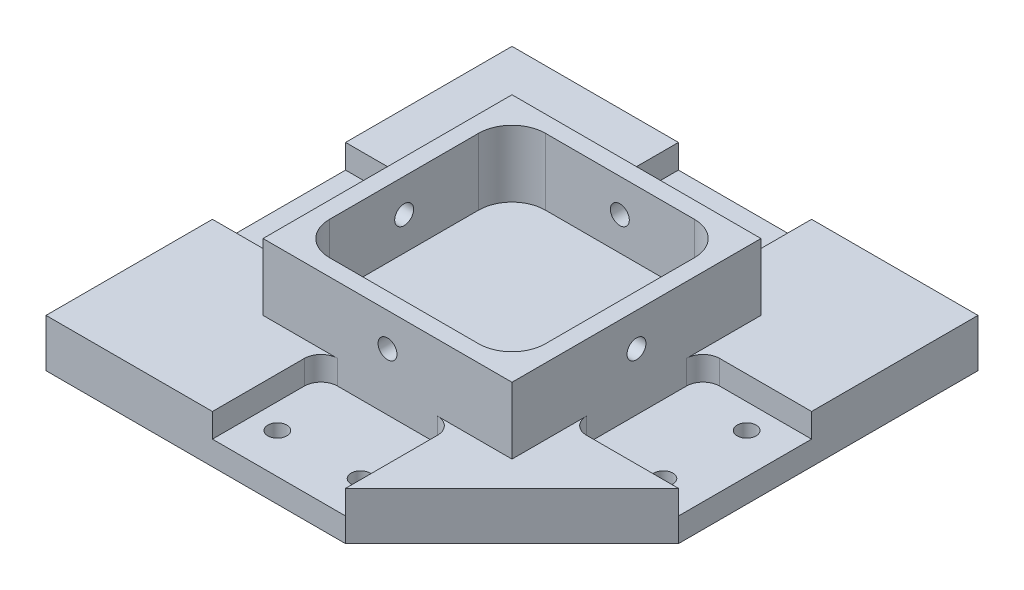
SolidWorks part; units mm, degrees
material "6061 Alloy"
ref_plane "Front Plane" through (0, 0, 0) normal (0, 0, 1) x (1, 0, 0)
ref_plane "Top Plane" through (0, 0, 0) normal (0, 1, 0) x (1, 0, 0)
ref_plane "Right Plane" through (0, 0, 0) normal (1, 0, 0) x (0, 0, -1)
sketch "Sketch1" plane through (0, 0, 0) normal (0, 1, 0) x (1, 0, 0)
  line L1 (0, 0) -> (88.9, 0)
  line L2 (0, 0) -> (0, 88.9)
  line L3 (0, 88.9) -> (88.9, 88.9)
  line L4 (88.9, 0) -> (88.9, 88.9)
  dimension "D1" = 88.9
  dimension "D2" = 88.9
extrude "Boss-Extrude1" add sketch "Sketch1" along normal blind 9.144
sketch "Sketch2" plane through (0, 9.144, 0) normal (0, 1, 0) x (1, 0, 0)
  line L0 (88.9, 88.9) -> (0, 88.9) construction
  line L1 (31.75, 88.9) -> (57.15, 88.9)
  line L2 (31.75, 88.9) -> (31.75, 67.31)
  line L3 (31.75, 67.31) -> (57.15, 67.31)
  line L4 (57.15, 88.9) -> (57.15, 67.31)
  line L5 (0, 88.9) -> (0, 0) construction
  line L6 (0, 57.15) -> (21.59, 57.15)
  line L7 (0, 57.15) -> (0, 31.75)
  line L8 (0, 31.75) -> (21.59, 31.75)
  line L9 (21.59, 57.15) -> (21.59, 31.75)
  line L10 (0, 0) -> (88.9, 0) construction
  line L11 (31.75, 0) -> (57.15, 0)
  line L12 (31.75, 0) -> (31.75, 21.59)
  line L13 (31.75, 21.59) -> (57.15, 21.59)
  line L14 (57.15, 0) -> (57.15, 21.59)
  line L15 (88.9, 0) -> (88.9, 88.9) construction
  line L16 (88.9, 57.15) -> (67.31, 57.15)
  line L17 (88.9, 57.15) -> (88.9, 31.75)
  line L18 (88.9, 31.75) -> (67.31, 31.75)
  line L19 (67.31, 57.15) -> (67.31, 31.75)
  dimension "D1" = 31.75
  dimension "D2" = 25.4
  dimension "D3" = 25.4
  dimension "D4" = 31.75
  dimension "D5" = 25.4
  dimension "D6" = 31.75
  dimension "D7" = 25.4
  dimension "D8" = 31.75
  dimension "D9" = 21.59
  dimension "D10" = 21.59
  dimension "D11" = 21.59
  dimension "D12" = 21.59
extrude "Cut-Extrude1" cut sketch "Sketch2" against normal blind 4.572
sketch "Sketch3" plane through (0, 9.144, 0) normal (0, 1, 0) x (1, 0, 0)
  line L0 (31.75, 88.9) -> (0, 88.9) construction
  line L1 (20.6375, 68.2625) -> (68.2625, 68.2625)
  line L2 (20.6375, 68.2625) -> (20.6375, 20.6375)
  line L3 (20.6375, 20.6375) -> (68.2625, 20.6375)
  line L4 (68.2625, 68.2625) -> (68.2625, 20.6375)
  line L5 (0, 31.75) -> (0, 0) construction
  line L6 (88.9, 31.75) -> (88.9, 57.15) construction
  line L7 (57.15, 88.9) -> (31.75, 88.9) construction
  line L8 (0, 57.15) -> (0, 31.75) construction
  line L9 (31.75, 0) -> (57.15, 0) construction
  circle A0 centre (28.194, 44.45) radius 2.4
  circle A1 centre (44.45, 60.706) radius 2.4
  circle A2 centre (60.706, 44.45) radius 2.4
  circle A3 centre (44.45, 28.194) radius 2.4
  dimension "D5" = 4.8
  dimension "D6" = 4.8
  dimension "D7" = 4.8
  dimension "D8" = 4.8
  dimension "D1" = 47.625
  dimension "D2" = 47.625
  dimension "D3" = 20.6375
  dimension "D4" = 20.6375
  dimension "D9" = 28.194
  dimension "D10" = 28.194
  dimension "D11" = 28.194
  dimension "D12" = 28.194
  dimension "D13" = 23.8125
  dimension "D14" = 23.8125
  dimension "D15" = 23.8125
  dimension "D16" = 23.8125
extrude "Cut-Extrude2" [suppressed] cut sketch "Sketch3" against normal through all contours A2 | A1 | A0 | A3
sketch "Sketch4" plane through (0, 4.572, 0) normal (0, 1, 0) x (1, 0, 0)
  line L0 (0, 57.15) -> (0, 31.75) construction
  line L1 (57.15, 88.9) -> (31.75, 88.9) construction
  line L2 (88.9, 31.75) -> (88.9, 57.15) construction
  line L3 (31.75, 0) -> (57.15, 0) construction
  line L4 (0, 31.75) -> (21.59, 31.75) construction
  line L5 (31.75, 21.59) -> (31.75, 0) construction
  line L6 (67.31, 31.75) -> (88.9, 31.75) construction
  line L7 (57.15, 67.31) -> (57.15, 88.9) construction
  circle A0 centre (81.28, 52.3875) radius 1.8034
  circle A1 centre (81.28, 36.5125) radius 1.8034
  circle A2 centre (52.3875, 81.28) radius 1.8034
  circle A3 centre (36.5125, 81.28) radius 1.8034
  circle A4 centre (7.62, 52.3875) radius 1.8034
  circle A5 centre (7.62, 36.5125) radius 1.8034
  circle A6 centre (36.5125, 7.62) radius 1.8034
  circle A7 centre (52.3875, 7.62) radius 1.8034
  dimension "D1" = 3.6068
  dimension "D2" = 3.6068
  dimension "D3" = 3.6068
  dimension "D4" = 3.6068
  dimension "D5" = 3.6068
  dimension "D6" = 3.6068
  dimension "D7" = 3.6068
  dimension "D8" = 3.6068
  dimension "D9" = 7.62
  dimension "D10" = 7.62
  dimension "D11" = 7.62
  dimension "D12" = 7.62
  dimension "D13" = 7.62
  dimension "D14" = 7.62
  dimension ".313" = 7.62
  dimension "D16" = 7.62
  dimension "D17" = 15.875
  dimension "D18" = 4.7625
  dimension "D19" = 4.7625
  dimension "D20" = 15.875
  dimension "D21" = 4.7625
  dimension "D22" = 15.875
  dimension "D23" = 4.7625
  dimension "D24" = 15.875
extrude "Cut-Extrude3" cut sketch "Sketch4" against normal through all
sketch "Sketch5" plane through (0, 9.144, 0) normal (0, 1, 0) x (1, 0, 0)
  line L0 (88.9, 88.9) -> (57.15, 88.9) construction
  line L1 (88.9, 31.75) -> (88.9, 57.15) construction
  circle A0 centre (44.45, 44.45) radius 6.35
  dimension "D1" = 12.7
  dimension "D2" = 44.45
  dimension "D3" = 44.45
extrude "Cut-Extrude4" [suppressed] cut sketch "Sketch5" against normal through all
sketch "Sketch6" plane through (0, 9.144, 0) normal (0, 1, 0) x (1, 0, 0)
  line L0 (88.9, 31.75) -> (57.15, 0)
  line L1 (57.15, 0) -> (88.9, 0)
  line L2 (88.9, 0) -> (88.9, 31.75)
extrude "Cut-Extrude5" cut sketch "Sketch6" against normal through all
sketch "Sketch7" plane through (0, 9.144, 0) normal (0, 1, 0) x (1, 0, 0)
  line L0 (0, 88.9) -> (0, 57.15) construction
  line L1 (20.701, 68.199) -> (68.199, 68.199)
  line L2 (20.701, 68.199) -> (20.701, 20.701)
  line L3 (20.701, 20.701) -> (68.199, 20.701)
  line L4 (68.199, 68.199) -> (68.199, 20.701)
  line L5 (0, 0) -> (31.75, 0) construction
  line L7 (23.876, 23.876) -> (65.024, 23.876)
  line L8 (23.876, 23.876) -> (23.876, 65.024)
  line L9 (23.876, 65.024) -> (65.024, 65.024)
  line L10 (65.024, 23.876) -> (65.024, 65.024)
  dimension "D1" = 47.498
  dimension "D2" = 47.498
  dimension "D3" = 20.701
  dimension "D4" = 20.701
  dimension "D5" = 3.175
  dimension "D6" = 3.175
  dimension "D7" = 3.175
  dimension "D8" = 3.175
extrude "Boss-Extrude2" add sketch "Sketch7" along normal blind 12.7 and the other way up to next (4.572 mm away)
fillet "Fillet9" radius 6.35 1 edges at (65.024, 15.494, -23.876)
fillet "Fillet10" radius 6.35 1 edges at (23.876, 15.494, -23.876)
fillet "Fillet11" radius 6.35 1 edges at (65.024, 15.494, -65.024)
fillet "Fillet12" radius 6.35 1 edges at (23.876, 15.494, -65.024)
fillet "Fillet15" radius 3.175 1 edges at (20.701, 6.858, -57.15)
fillet "Fillet16" radius 3.175 1 edges at (31.75, 6.858, -20.701)
fillet "Fillet17" radius 3.175 1 edges at (57.15, 6.858, -20.701)
fillet "Fillet18" radius 3.175 1 edges at (68.199, 6.858, -57.15)
fillet "Fillet19" radius 3.175 1 edges at (68.199, 6.858, -31.75)
fillet "Fillet20" radius 3.175 1 edges at (31.75, 6.858, -68.199)
fillet "Fillet21" radius 3.175 1 edges at (57.15, 6.858, -68.199)
fillet "Fillet22" radius 3.175 1 edges at (20.701, 6.858, -31.75)
sketch "Sketch9" plane through (0, 0, -68.199) normal (0, 0, -1) x (-1, 0, 0)
  line L0 (-68.199, 21.844) -> (-68.199, 9.144) construction
  line L1 (-68.199, 21.844) -> (-20.701, 21.844) construction
  circle A0 centre (-44.45, 15.494) radius 1.8034
  dimension "D1" = 3.6068
  dimension "D2" = 23.749
  dimension "D3" = 6.35
extrude "Cut-Extrude6" cut sketch "Sketch9" against normal through all
sketch "Sketch10" plane through (68.199, 0, 0) normal (1, 0, 0) x (0, 0, -1)
  line L0 (20.701, 21.844) -> (68.199, 21.844) construction
  line L1 (20.701, 21.844) -> (20.701, 9.144) construction
  circle A0 centre (44.45, 15.494) radius 1.8034
  dimension "D1" = 3.6068
  dimension "D2" = 6.35
  dimension "D3" = 23.749
extrude "Cut-Extrude7" cut sketch "Sketch10" against normal through all
equation "\"hinge_hole\"= 0.142in"
equation "\"D1@Sketch4\"=\"hinge_hole\""
equation "\"D2@Sketch4\"=\"hinge_hole\""
equation "\"D3@Sketch4\"=\"hinge_hole\""
equation "\"D4@Sketch4\"=\"hinge_hole\""
equation "\"D5@Sketch4\"=\"hinge_hole\""
equation "\"D6@Sketch4\"=\"hinge_hole\""
equation "\"D7@Sketch4\"=\"hinge_hole\""
equation "\"D8@Sketch4\"=\"hinge_hole\""
equation "\"hinge_hole_dist\"= 0.297 + 0.25"
equation "\".313@Sketch4\"=.3"
equation "\"hinge_hole_sep\"= 0.625"
equation "\"hinge_hole_from_wall\"= ( 1 - \"hinge_hole_sep\" ) / 2"
equation "\"D17@Sketch4\"=\"hinge_hole_sep\""
equation "\"D18@Sketch4\"=\"hinge_hole_from_wall\""
equation "\"D19@Sketch4\"=\"hinge_hole_from_wall\""
equation "\"D20@Sketch4\"=\"hinge_hole_sep\""
equation "\"D21@Sketch4\"=\"hinge_hole_from_wall\""
equation "\"D22@Sketch4\"=\"hinge_hole_sep\""
equation "\"D23@Sketch4\"=\"hinge_hole_from_wall\""
equation "\"D24@Sketch4\"=\"hinge_hole_sep\""
equation "\"D9@Sketch2\"=\"hinge_hole_dist\" + (0.6-0.297)"
equation "\"D12@Sketch2\"=\"hinge_hole_dist\" + (0.6-0.297)"
equation "\"D11@Sketch2\"=\"hinge_hole_dist\" + (0.6-0.297)"
equation "\"D10@Sketch2\"=\"hinge_hole_dist\" + (0.6-0.297)"
